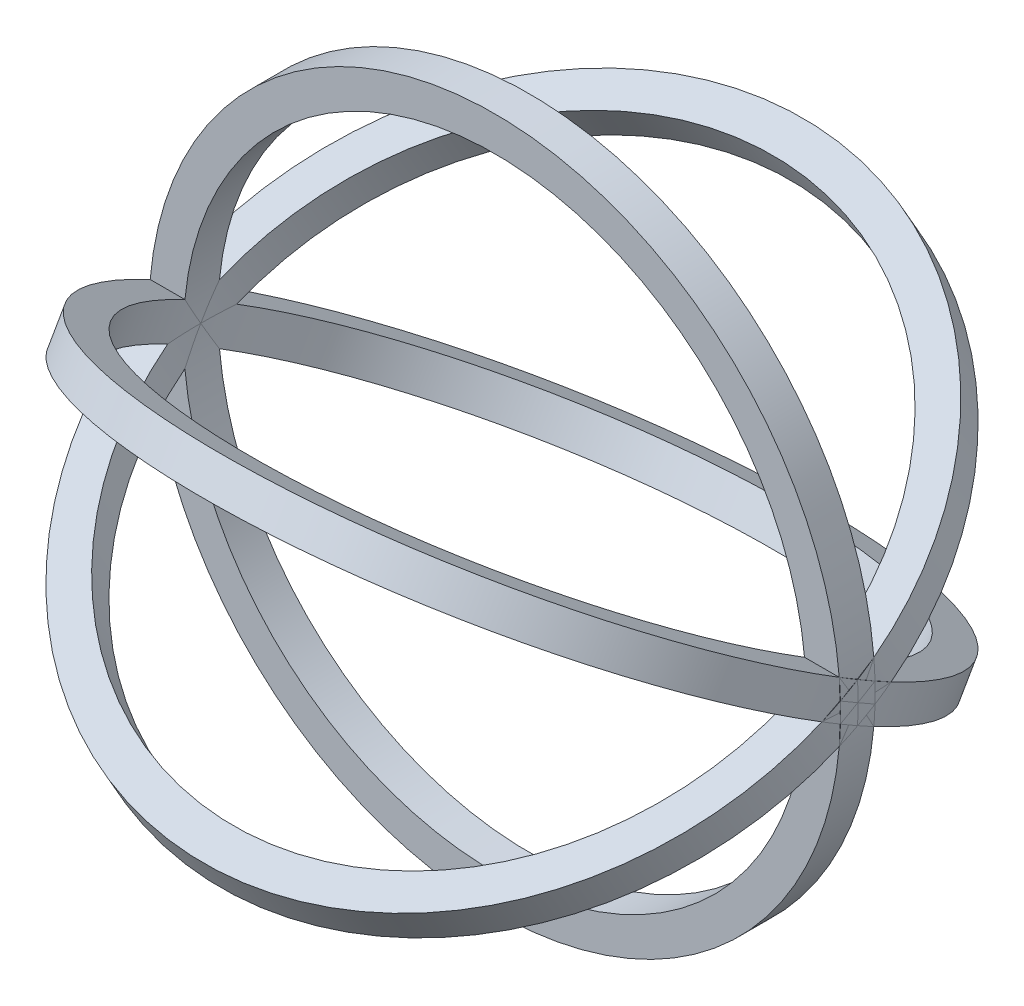
SolidWorks part; units mm, degrees
ref_plane "Front Plane" through (0, 0, 0) normal (0, 0, 1) x (1, 0, 0)
ref_plane "Top Plane" through (0, 0, 0) normal (0, 1, 0) x (1, 0, 0)
ref_plane "Right Plane" through (0, 0, 0) normal (1, 0, 0) x (0, 0, -1)
sketch "Sketch1" plane through (0, 0, 0) normal (0, 0, 1) x (1, 0, 0)
  circle A0 centre (0, 0) radius 15
  circle A1 centre (0, 0) radius 13.5
  dimension "D1" = 30
  dimension "D2" = 1.5
extrude "Boss-Extrude1" add sketch "Sketch1" along normal mid plane 1.5
ref_axis "Axis1" through (16.5, 0, 0) along (-1, 0, 0)
pattern_circular "CirPattern1" count 6 over 360 about axis through (16.5, 0, 0) along (-1, 0, 0) of "Boss-Extrude1"
equation "\"D\"= 30mm"
equation "\"D1@Sketch1\"=\"D\""
equation "\"D2@Sketch1\"=\"D\"/20"
equation "\"D1@Boss-Extrude1\"=\"D\"/20"
